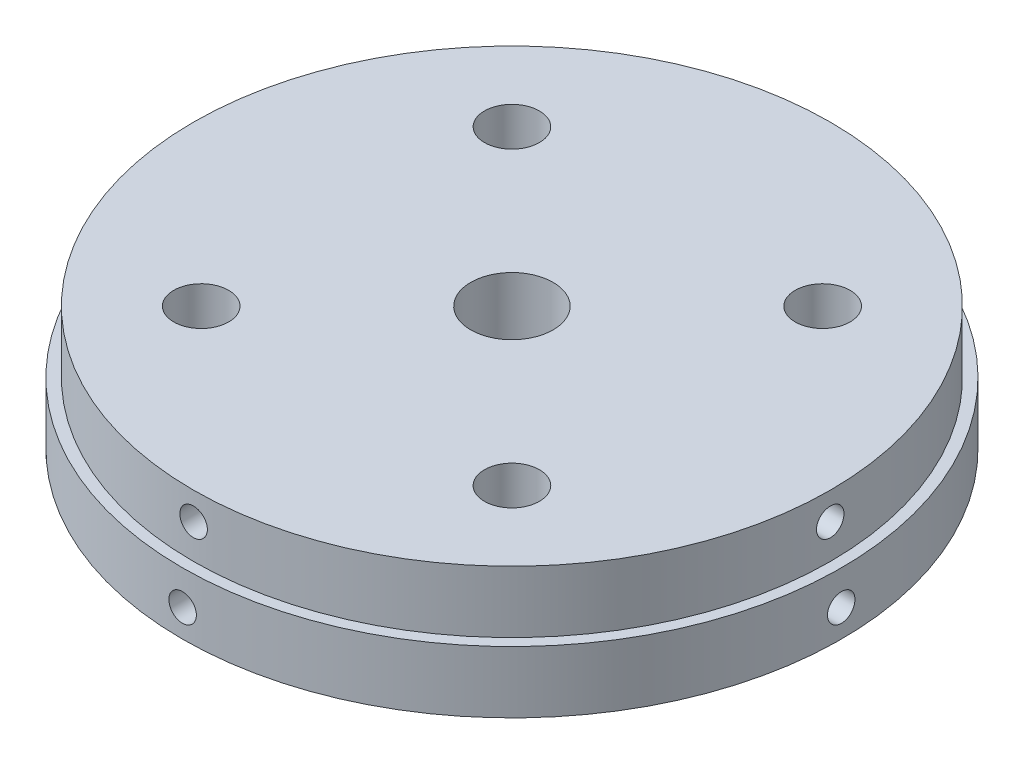
SolidWorks part; units mm, degrees
material "6061-T6 (SS)"
ref_plane "Front Plane" through (0, 0, 0) normal (0, 0, 1) x (1, 0, 0)
ref_plane "Top Plane" through (0, 0, 0) normal (0, 1, 0) x (1, 0, 0)
ref_plane "Right Plane" through (0, 0, 0) normal (1, 0, 0) x (0, 0, -1)
sketch "Sketch1" plane through (0, 0, 0) normal (0, 1, 0) x (1, 0, 0)
  circle A0 centre (0, 0) radius 76.2
  dimension "D1" = 152.4
extrude "Boss-Extrude1" add sketch "Sketch1" along normal blind 28.575
sketch "Sketch2" plane through (0, 28.575, 0) normal (0, 1, 0) x (1, 0, 0)
  circle A0 centre (0, 0) radius 9.525
  dimension "D1" = 19.05
extrude "Cut-Extrude1" cut sketch "Sketch2" against normal through all
ref_plane "Plane1" through (0, 0, 76.2) normal (0, 0, 1) x (1, 0, 0)
ref_plane "Plane2" through (0, 0, -69.85) normal (0, 0, 1) x (1, 0, 0)
sketch "Sketch30" plane through (0, 0, 76.2) normal (0, 0, 1) x (1, 0, 0)
  line L0 (0, 30.5674) -> (0, -2.7265) construction
  line L1 (76.2, 28.575) -> (-76.2, 28.575) construction
  circle A0 centre (0, 22.225) radius 3.175
  circle A1 centre (0, 6.35) radius 3.175
  dimension "D1" = 6.35
  dimension "D2" = 6.35
  dimension "D3" = 15.875
  dimension "D4" = 6.35
extrude "Cut-Extrude2" cut sketch "Sketch30" against normal blind 25.4
pattern_circular "CirPattern3" count 4 over 360 about axis through (0, 28.575, 0) along (0, -1, 0) of "Cut-Extrude2" reverse direction yes
sketch "Sketch31" plane through (0, 28.575, 0) normal (0, 1, 0) x (1, 0, 0)
  line L0 (0, 76.2) -> (0, -76.2) construction
  line L1 (-76.2, 0) -> (76.2, 0) construction
  line L2 (53.8815, 53.8815) -> (-53.8815, -53.8815) construction
  line L3 (-53.8815, 53.8815) -> (53.8815, -53.8815) construction
  circle A0 centre (0, 0) radius 76.2 construction
  circle A1 centre (35.921, 35.921) radius 6.35
  dimension "D4" = 12.7
  dimension "D1" = 50.8
  dimension "D2" = 45
  dimension "D3" = 45
extrude "Cut-Extrude3" cut sketch "Sketch31" against normal through all
pattern_circular "CirPattern4" count 4 over 360 about axis through (0, 28.575, 0) along (0, -1, 0) of "Cut-Extrude3"
ref_axis "Axis1" through (0, 28.575, 0) along (0, -1, 0)
sketch "Sketch34" plane through (0, 0, 0) normal (0, 0, 1) x (1, 0, 0)
  line L1 (76.2, 28.575) -> (73.66, 28.575)
  line L2 (76.2, 28.575) -> (76.2, 14.2875)
  line L3 (76.2, 14.2875) -> (73.66, 14.2875)
  line L4 (73.66, 28.575) -> (73.66, 14.2875)
  dimension "D1" = 14.2875
  dimension "D2" = 2.54
revolve "Cut-Revolve1" cut sketch "Sketch34" angle 360 about axis through (0, 28.575, 0) along (0, -1, 0)
